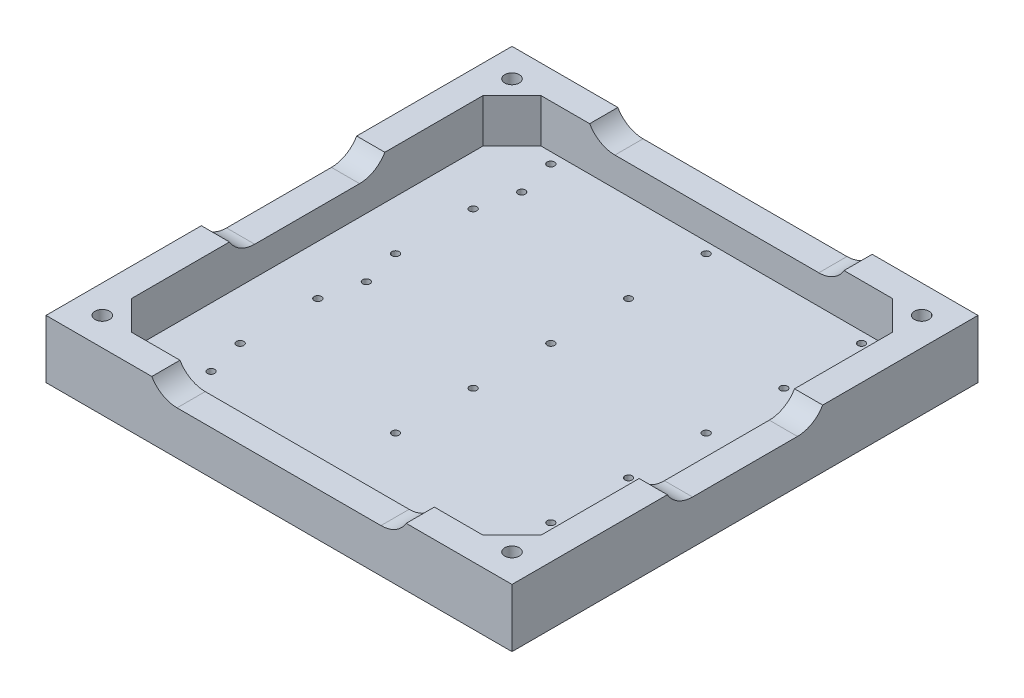
SolidWorks part; units mm, degrees
ref_plane "Front Plane" through (0, 0, 0) normal (0, 0, 1) x (1, 0, 0)
ref_plane "Top Plane" through (0, 0, 0) normal (0, 1, 0) x (1, 0, 0)
ref_plane "Right Plane" through (0, 0, 0) normal (1, 0, 0) x (0, 0, -1)
sketch "Sketch1" plane through (0, 0, 0) normal (0, 1, 0) x (1, 0, 0)
  line L0 (-31.25, 0) -> (-0.75, 0) construction
  line L1 (0.75, 0) -> (31.25, 0) construction
  line L2 (0, 0.75) -> (0, 8) construction
  line L3 (-48, 8) -> (48, 8)
  line L4 (-48, 8) -> (-48, -88)
  line L5 (-48, -88) -> (48, -88)
  line L6 (48, 8) -> (48, -88)
  line L7 (32.75, 0) -> (48, 0) construction
  line L8 (0, -80.75) -> (0, -88) construction
  line L9 (0, -0.75) -> (0, -15.25) construction
  circle A0 centre (0, 0) radius 0.75
  circle A1 centre (32, 0) radius 0.75
  circle A2 centre (-32, 0) radius 0.75
  circle A3 centre (0, -16) radius 0.75
  circle A4 centre (-32, -16) radius 0.75
  circle A5 centre (32, -16) radius 0.75
  circle A6 centre (0, -32) radius 0.75
  circle A7 centre (-32, -32) radius 0.75
  circle A8 centre (32, -32) radius 0.75
  circle A9 centre (0, -48) radius 0.75
  circle A10 centre (-32, -48) radius 0.75
  circle A11 centre (32, -48) radius 0.75
  circle A12 centre (0, -64) radius 0.75
  circle A13 centre (-32, -64) radius 0.75
  circle A14 centre (32, -64) radius 0.75
  circle A15 centre (0, -80) radius 0.75
  circle A16 centre (-32, -80) radius 0.75
  circle A17 centre (32, -80) radius 0.75
  point P19 (0, -88)
  dimension "D1" = 1.5
  dimension "D2" = 8
  dimension "D3" = 16
  dimension "D4" = 30.5
  dimension "D6" = 14.5
  dimension "D5" = 6
extrude "Boss-Extrude1" add sketch "Sketch1" along normal blind 3
sketch "Sketch2" plane through (0, 3, 0) normal (0, 1, 0) x (1, 0, 0)
  line L0 (-36.2, 2.2) -> (36.2, 2.2)
  line L1 (-48, 8) -> (48, 8)
  line L2 (-48, 8) -> (-48, -88)
  line L3 (-48, -88) -> (48, -88)
  line L4 (48, 8) -> (48, -88)
  line L5 (42.2, -3.8) -> (42.2, -76.2)
  line L6 (-36.2, -82.2) -> (36.2, -82.2)
  line L7 (-42.2, -3.8) -> (-42.2, -76.2)
  line L8 (-42.2, 2.2) -> (42.2, 2.2) construction
  line L9 (-42.2, 2.2) -> (-42.2, -82.2) construction
  line L10 (-42.2, -3.8) -> (-36.2, 2.2)
  line L11 (42.2, 2.2) -> (42.2, -82.2) construction
  line L12 (36.2, 2.2) -> (42.2, -3.8)
  line L13 (-42.2, -82.2) -> (42.2, -82.2) construction
  line L14 (42.2, -76.2) -> (36.2, -82.2)
  line L15 (-42.2, -76.2) -> (-36.2, -82.2)
  line L16 (-48, -88) -> (48, -88) construction
  circle A1 centre (32, -80) radius 0.75 construction
  point P5 (0, 0)
  point P18 (0, 0)
  point P21 (48, -88)
  dimension "D2" = 6
  dimension "D3" = 6
  dimension "D4" = 6
  dimension "D5" = 16
  dimension "D1" = 5.8
extrude "Boss-Extrude2" add sketch "Sketch2" along normal blind 9
sketch "Sketch3" plane through (0, 12, 0) normal (0, 1, 0) x (1, 0, 0)
  line L0 (-42.2, 2.2) -> (-39.2, -0.8) construction
  line L1 (-36.2, 2.2) -> (-42.2, -3.8) construction
  line L2 (-36.2, 2.2) -> (-42.2, -3.8) construction
  line L3 (39.2, -0.8) -> (42.2, 2.2) construction
  line L4 (42.2, -3.8) -> (36.2, 2.2) construction
  line L5 (39.2, -79.2) -> (42.2, -82.2) construction
  line L6 (36.2, -82.2) -> (42.2, -76.2) construction
  line L7 (-39.2, -79.2) -> (-42.2, -82.2) construction
  line L8 (-42.2, -76.2) -> (-36.2, -82.2) construction
  line L9 (-42.2, -76.2) -> (-36.2, -82.2) construction
  line L10 (-36.2, -82.2) -> (36.2, -82.2) construction
  line L11 (-42.2, 2.2) -> (42.2, 2.2) construction
  line L12 (-42.2, 2.2) -> (-42.2, -82.2) construction
  line L13 (-42.2, -82.2) -> (42.2, -82.2) construction
  line L14 (42.2, 2.2) -> (42.2, -82.2) construction
  circle A0 centre (-42.2, 2.2) radius 1.5
  circle A1 centre (42.2, 2.2) radius 1.5
  circle A2 centre (42.2, -82.2) radius 1.5
  circle A3 centre (-42.2, -82.2) radius 1.5
  dimension "D1" = 3
extrude "Cut-Extrude1" cut sketch "Sketch3" against normal up to surface (9 mm away) up to face at (0, 3, 40)
sketch "Sketch4" plane through (0, 0, 88) normal (0, 0, 1) x (1, 0, 0)
  line L0 (-26.2, 12) -> (26.2, 12)
  line L2 (-21.0038, 9) -> (21.0038, 9)
  line L5 (-48, 12) -> (48, 12) construction
  arc A0 (-26.2, 12) -> (-21.0038, 9) centre (-21.0038, 15) ccw
  arc A1 (21.0038, 9) -> (26.2, 12) centre (21.0038, 15) ccw
  point P13 (0, 12)
  point P17 (0, 12)
  dimension "D1" = 6
  dimension "D2" = 3
  dimension "D3" = 10
extrude "Cut-Extrude2" cut sketch "Sketch4" against normal through all
sketch "Sketch5" plane through (-48, 0, 0) normal (-1, 0, 0) x (0, 0, 1)
  line L0 (-8, 12) -> (88, 12) construction
  line L1 (29.1962, 9) -> (50.8038, 9)
  line L2 (24, 12) -> (56, 12)
  line L3 (40, 9) -> (40, 0) construction
  line L4 (-8, 0) -> (88, 0) construction
  arc A0 (24, 12) -> (29.1962, 9) centre (29.1962, 15) ccw
  arc A1 (56, 12) -> (50.8038, 9) centre (50.8038, 15) cw
  point P8 (40, 9)
  point P9 (40, 12)
  dimension "D2" = 6
  dimension "D1" = 32
  dimension "D3" = 3
extrude "Cut-Extrude3" cut sketch "Sketch5" against normal through all
sketch "Sketch6" plane through (0, 3, 0) normal (0, 1, 0) x (1, 0, 0)
  line L0 (-31.25, -64) -> (-31.25, -72) construction
  line L1 (-31.25, -72) -> (-30.75, -72) construction
  line L2 (-32, -64) -> (-31.25, -64) construction
  circle A0 centre (-30, -72) radius 0.75
  circle A1 centre (-32, -64) radius 0.75 construction
  dimension "D1" = 8
  dimension "D2" = 0.5
extrude "Cut-Extrude4" cut sketch "Sketch6" against normal through all
pattern_linear "LPattern4" count 3 spacing 32 along (0, 0, -1) of "Cut-Extrude4"
